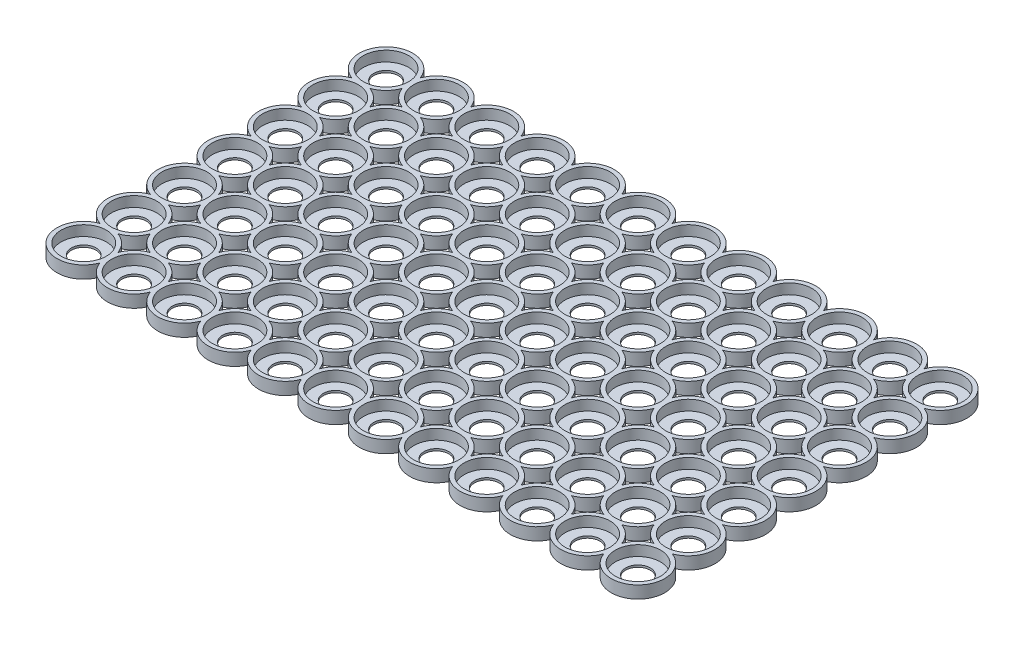
SolidWorks part; units mm, degrees
ref_plane "Front Plane" through (0, 0, 0) normal (0, 0, 1) x (1, 0, 0)
ref_plane "Top Plane" through (0, 0, 0) normal (0, 1, 0) x (1, 0, 0)
ref_plane "Right Plane" through (0, 0, 0) normal (1, 0, 0) x (0, 0, -1)
sketch "Sketch1" plane through (0, 0, 0) normal (1, 0, 0) x (0, 0, -1)
  line L0 (0, 27.0772) -> (0, -22.0037) construction
  line L1 (-13, 3) -> (-13, -3)
  line L2 (-13, -3) -> (-6, -3)
  line L3 (-6, -3) -> (-6, -2)
  line L4 (-6, -2) -> (-11, -2)
  line L5 (-11, -2) -> (-11, 3)
  line L6 (-11, 3) -> (-13, 3)
  point P5 (-13, 0)
  dimension "D1" = 6
  dimension "D2" = 1
  dimension "D3" = 22
  dimension "D4" = 12
  dimension "D5" = 2
revolve "Revolve1" add sketch "Sketch1" angle 360 about L0
sketch "Sketch2" plane through (0, -3, 0) normal (0, -1, 0) x (1, 0, 0)
  line L0 (0, 12.1827) -> (0, -11.4982) construction
pattern_linear "LPattern1" count 7 spacing 24.5 along (0, 0, -1) of "Revolve1"
sketch "Sketch3" plane through (0, -3, 0) normal (0, -1, 0) x (1, 0, 0)
  line L0 (-17.2986, 0) -> (17.8169, 0) construction
pattern_linear "LPattern2" count 12 spacing 24.5 along (1, 0, 0) of "Revolve1", "LPattern1"
